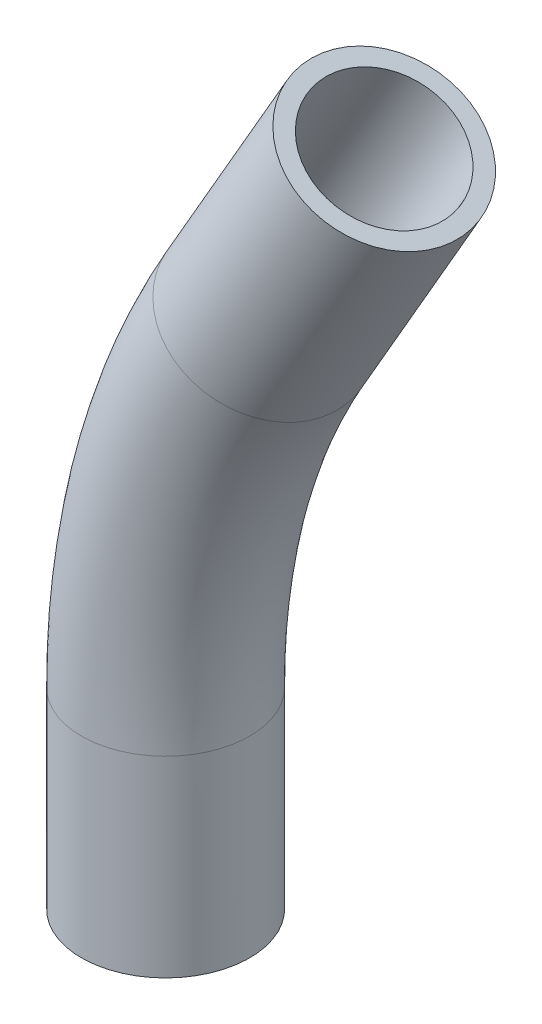
SolidWorks part; units mm, degrees
material "PVC Rigid"
ref_plane "front" through (0, 0, 0) normal (0, 0, 1) x (1, 0, 0)
ref_plane "top" through (0, 0, 0) normal (0, 1, 0) x (1, 0, 0)
ref_plane "side" through (0, 0, 0) normal (1, 0, 0) x (0, 0, -1)
sketch "ElbowArc" plane through (0, 0, 0) normal (0, 0, 1) x (1, 0, 0)
  arc A0 (-146.05, 0) -> (-126.483, 73.025) centre (0, 0) cw
  dimension "BendAngle" = 30
  dimension "BendRadius" = 146.05
sketch "Route" plane through (0, 0, 0) normal (0, 1, 0) x (1, 0, 0)
  circle A0 centre (-146.05, 0) radius 16.7005
  dimension "ElbowOD" = 33.401
  dimension "BendRadius" = 146.05
sweep "Elbow" add profiles "Route" path "ElbowArc"
sketch3d "3DSketch3"
  circle A0 centre (-126.483, 73.025, 0) radius 16.7005 construction
  point P0 (-126.483, 73.025, 0)
  point P3 (-118.1328, 87.4881, 0)
sketch3d "3DSketch4"
  circle A0 centre (-146.05, 0, 0) radius 16.7005 construction
  point P0 (-146.05, 0, 0)
  point P3 (-146.05, 16.7005, 0)
other "CPoint1" parameters "Diameter"=25.4, "StubLength"=0
ref_axis "Axis1" through (-146.05, -10, 0) along (0, 1, 0)
other "CPoint2" parameters "Diameter"=25.4, "StubLength"=0
ref_axis "Axis2" through (-121.483, 81.6853, 0) along (-0.5, -0.866, 0)
other "RPoint1"
shell "ElbowShell" thickness 3.3782 removed face at (-126.483, 73.025, 16.7005) removed face at (-146.05, 0, 16.7005)
sketch "Sketch2" plane through (0, 0, 0) normal (0.5, 0.866, 0) x (-0.866, 0.5, 0)
  circle A0 centre (146.05, 0) radius 16.7005 construction
  circle A1 centre (146.05, 0) radius 13.3223 construction
  circle A2 centre (146.05, 0) radius 16.7005
  circle A3 centre (146.05, 0) radius 13.3223
extrude "ElbowExtension-Extrude1" add sketch "Sketch2" along normal blind 47.625
sketch "Sketch3" plane through (0, 0, 0) normal (0, -1, 0) x (1, 0, 0)
  circle A0 centre (-146.05, 0) radius 13.3223 construction
  circle A1 centre (-146.05, 0) radius 16.7005 construction
  circle A2 centre (-146.05, 0) radius 13.3223
  circle A3 centre (-146.05, 0) radius 16.7005
extrude "ElbowExtension-Extrude2" add sketch "Sketch3" along normal blind 38.1
